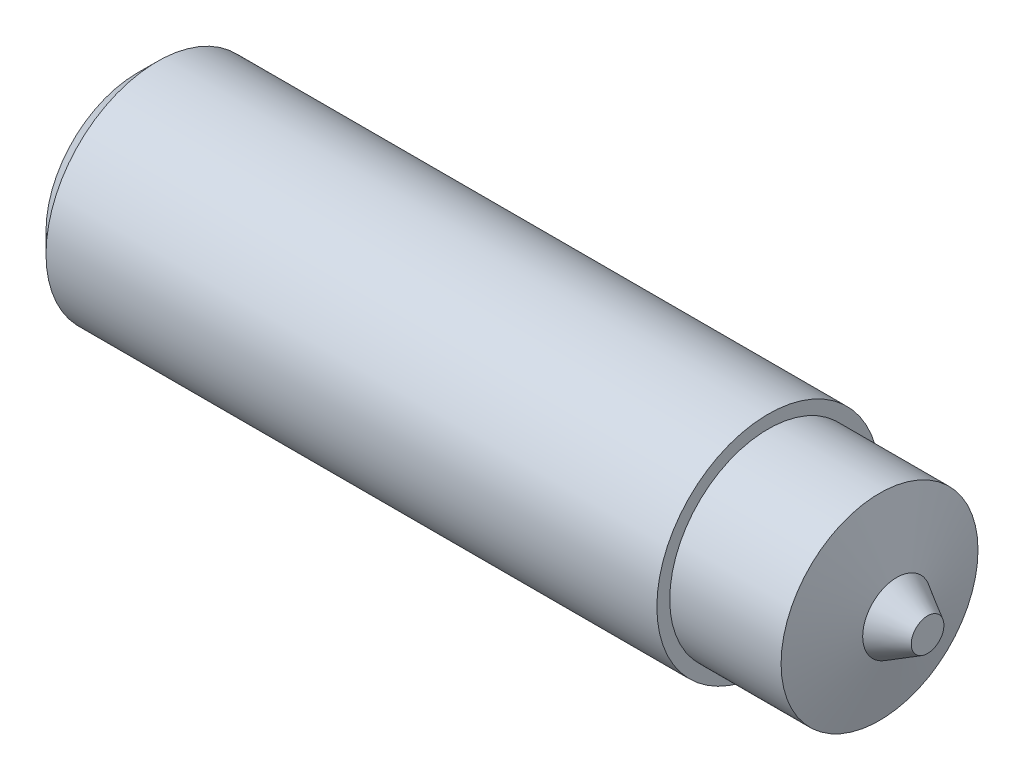
SolidWorks part; units mm, degrees
ref_plane "Front" through (0, 0, 0) normal (0, 0, 1) x (1, 0, 0)
ref_plane "Top" through (0, 0, 0) normal (0, 1, 0) x (1, 0, 0)
ref_plane "Right" through (0, 0, 0) normal (1, 0, 0) x (0, 0, -1)
sketch "Sketch1" plane through (0, 0, 0) normal (0, 0, 1) x (1, 0, 0)
  line L0 (-13.9509, 0) -> (13.0454, 0) construction
  line L1 (0, 0) -> (0, 3)
  line L2 (0, 3) -> (17, 3)
  line L3 (20, 2.6528) -> (20.4645, 0.9192)
  line L4 (17, 3) -> (19.907, 3) construction
  line L5 (17, 3) -> (17, 2.6528)
  line L6 (21.2945, 0.44) -> (21.2945, 0)
  line L7 (21.2945, 0) -> (0, 0)
  line L8 (21.2945, 0.44) -> (20.4645, 0.9192)
  line L9 (17, 2.6528) -> (20, 2.6528)
  dimension "D3" = 30
  dimension "D4" = 15
  dimension "D1" = 5.3055
  dimension "a" = 3
  dimension "l" = 20
revolve "Base" add sketch "Sketch1" angle 360 about L0
cosmetic thread "ThreadCosmetic1" [suppressed] parameters "D2"=4.917
chamfer "HeadChamfer" distance 0.5415 angle 45 1 edges at (0, 0, 3)
sketch "Sketch2" plane through (0, 0, 0) normal (0, 0, 1) x (1, 0, 0)
  line L0 (0.5415, 2.531) -> (0.8123, 3)
  line L1 (0.8123, 3) -> (0.8123, 3.5)
  line L2 (0.8123, 3.5) -> (0.2708, 3.5)
  line L3 (0.2708, 3.5) -> (0.2708, 3)
  line L4 (0.2708, 3) -> (0.5415, 2.531)
  line L5 (0, 0) -> (8.4815, 0) construction
  line L6 (0.5415, 3) -> (0.5415, -3) construction
  dimension "D1" = 60
  dimension "D2" = 0.5
  dimension "D3" = 0.5415
  dimension "D4" = 60
  dimension "D5" = 6
revolve "Cut-Revolve10" [suppressed] cut sketch "Sketch2" angle 360 about L5
pattern_linear "LPattern10" [suppressed] count 26 spacing 0.6498 along (1, 0, 0) of bodies 102
equation "\"D1@HeadChamfer\" =  ( \"d@Sketch1\" - \"D2@ThreadCosmetic1\" )  / 2"
equation "\"D5@Sketch2\" = \"d@Sketch1\""
equation "\"D3@Sketch2\" =  ( \"d@Sketch1\" - \"D2@ThreadCosmetic1\" )  / 2"
equation "\"D3@LPattern10\" = \"D3@Sketch2\" * 1.2"
equation "\"D1@LPattern10\" = (  \"l@Sketch1\" - \"a@Sketch1\" )  / \"D3@LPattern10\""
